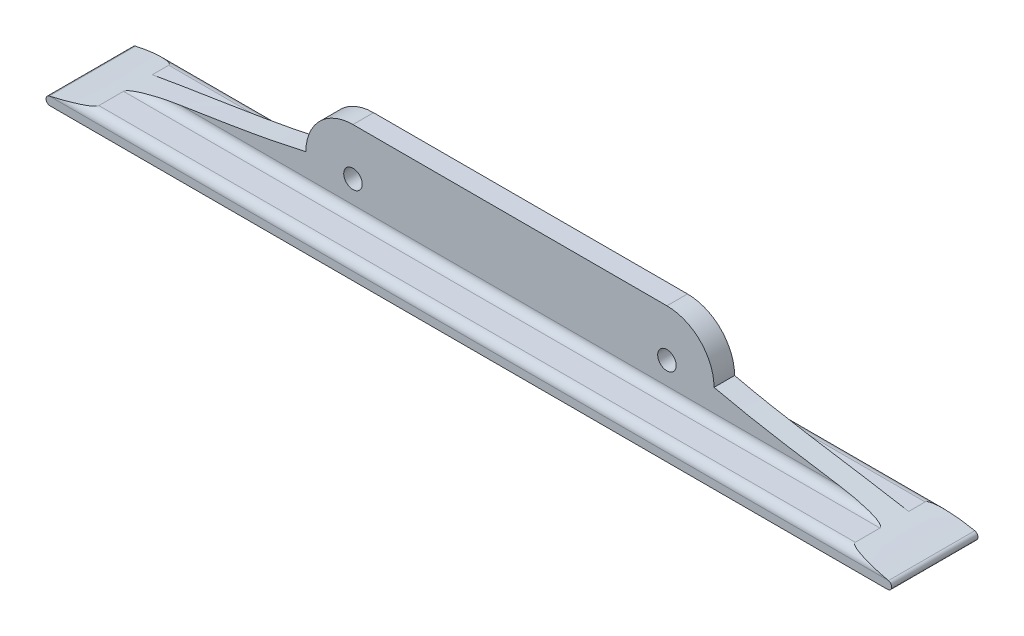
SolidWorks part; units mm, degrees
ref_plane "Front Plane" through (0, 0, 0) normal (0, 0, 1) x (1, 0, 0)
ref_plane "Top Plane" through (0, 0, 0) normal (0, 1, 0) x (1, 0, 0)
ref_plane "Right Plane" through (0, 0, 0) normal (1, 0, 0) x (0, 0, -1)
sketch "Sketch2" plane through (0, 0, 0) normal (0, 0, 1) x (1, 0, 0)
  line L0 (0, -20) -> (0, -10.2201) construction
  line L1 (-38.1799, -11.5638) -> (38.1799, -11.5638) construction
  line L2 (-38.1799, -0.1087) -> (38.1799, -0.1087)
  line L3 (-38.1799, -23.0188) -> (38.1799, -23.0188)
  line L4 (-101.839, -23.0188) -> (-38.1799, -23.0188)
  line L5 (101.839, -23.0188) -> (38.1799, -23.0188)
  circle A0 centre (-38.1799, -11.5638) radius 2.25
  arc A2 (-38.1799, -0.1087) -> (-49.635, -11.5638) centre (-38.1799, -11.5638) ccw
  arc A4 (-102.0579, -21.0431) -> (-101.839, -23.0188) centre (-101.839, -22.0188) ccw
  arc A5 (102.0579, -21.0431) -> (101.839, -23.0188) centre (101.839, -22.0188) cw
  arc A6 (38.1799, -0.1087) -> (49.635, -11.5638) centre (38.1799, -11.5638) cw
  circle A7 centre (38.1799, -11.5638) radius 2.25
  spline S0 degree 3 poles (-49.635, -11.5638) (-59.1557, -13.7815) (-76.7162, -16.4523) (-94.2528, -19.2925) (-102.0579, -21.0431) knots 0 0 0 0 0.476678 0.866805 0.866805 0.866805 0.866805
  spline S1 degree 3 poles (49.635, -11.5638) (59.1557, -13.7815) (76.7162, -16.4523) (94.2528, -19.2925) (102.0579, -21.0431) knots 0 0 0 0 0.476678 0.866805 0.866805 0.866805 0.866805
  point P2 (-1.4525, -11.5638)
  point P10 (1.4525, -11.5638)
  point P12 (0, -0.1087)
  point P17 (0, -11.5638)
  point P26 (0, -23.0188)
extrude "Boss-Extrude1" add sketch "Sketch2" along normal blind 5
sketch "Sketch3" plane through (0, 0, 5) normal (0, 0, 1) x (1, 0, 0)
  line L0 (-91.9852, -19.0188) -> (91.9852, -19.0188)
  line L2 (-101.839, -23.0188) -> (101.839, -23.0188)
  line L3 (38.1799, -0.1087) -> (-38.1799, -0.1087)
  line L4 (-101.839, -23.0188) -> (101.839, -23.0188)
  arc A4 (-102.0579, -21.0431) -> (-101.839, -23.0188) centre (-101.839, -22.0188) ccw
  arc A5 (101.839, -23.0188) -> (102.0579, -21.0431) centre (101.839, -22.0188) ccw
  arc A6 (49.635, -11.5638) -> (38.1799, -0.1087) centre (38.1799, -11.5638) ccw
  arc A7 (-38.1799, -0.1087) -> (-49.635, -11.5638) centre (-38.1799, -11.5638) ccw
  arc A8 (-102.0579, -21.0431) -> (-101.839, -23.0188) centre (-101.839, -22.0188) ccw
  arc A9 (101.839, -23.0188) -> (102.0579, -21.0431) centre (101.839, -22.0188) ccw
  spline S2 degree 3 poles (-425.669, 4952.2976) (277.9433, 21.7623) (-79.6725, 0.525) (-427.6269, -89.1346) (314.7787, -4981.0489) knots -8.266125 -8.266125 -8.266125 -8.266125 0.476678 9.159945 9.159945 9.159945 9.159945 only from (-49.635, -11.5638) to (-102.0579, -21.0431)
  spline S3 degree 3 poles (-314.7776, -4981.0419) (427.6267, -89.1346) (79.6718, 0.5252) (-277.9446, 21.7623) (425.6764, 4952.3499) knots -8.293136 -8.293136 -8.293136 -8.293136 0.390127 9.132961 9.132961 9.132961 9.132961 only from (102.0579, -21.0431) to (49.635, -11.5638)
  spline S4 degree 3 poles (-91.9852, -19.0188) (-95.3545, -19.6299) (-98.7142, -20.2931) (-102.0579, -21.0431) knots 0.699677 0.699677 0.699677 0.699677 0.866805 0.866805 0.866805 0.866805
  spline S5 degree 3 poles (102.0579, -21.0431) (98.7142, -20.2931) (95.3545, -19.6299) (91.9852, -19.0188) knots 0 0 0 0 0.167128 0.167128 0.167128 0.167128
  point P12 (83.7246, -17.5917)
  point P13 (83.8569, -17.6307)
  point P15 (89.624, -19.0188)
  point P17 (91.3955, -19.0188)
  dimension "D2" = 4
  dimension "D1" = 0
extrude "Boss-Extrude2" add sketch "Sketch3" along normal blind 10 and the other way blind 11
fillet "Fillet1" radius 2 3 edges at (0, -19.0188, -6) (0, -19.0188, 15) (0, -19.0188, 5)
